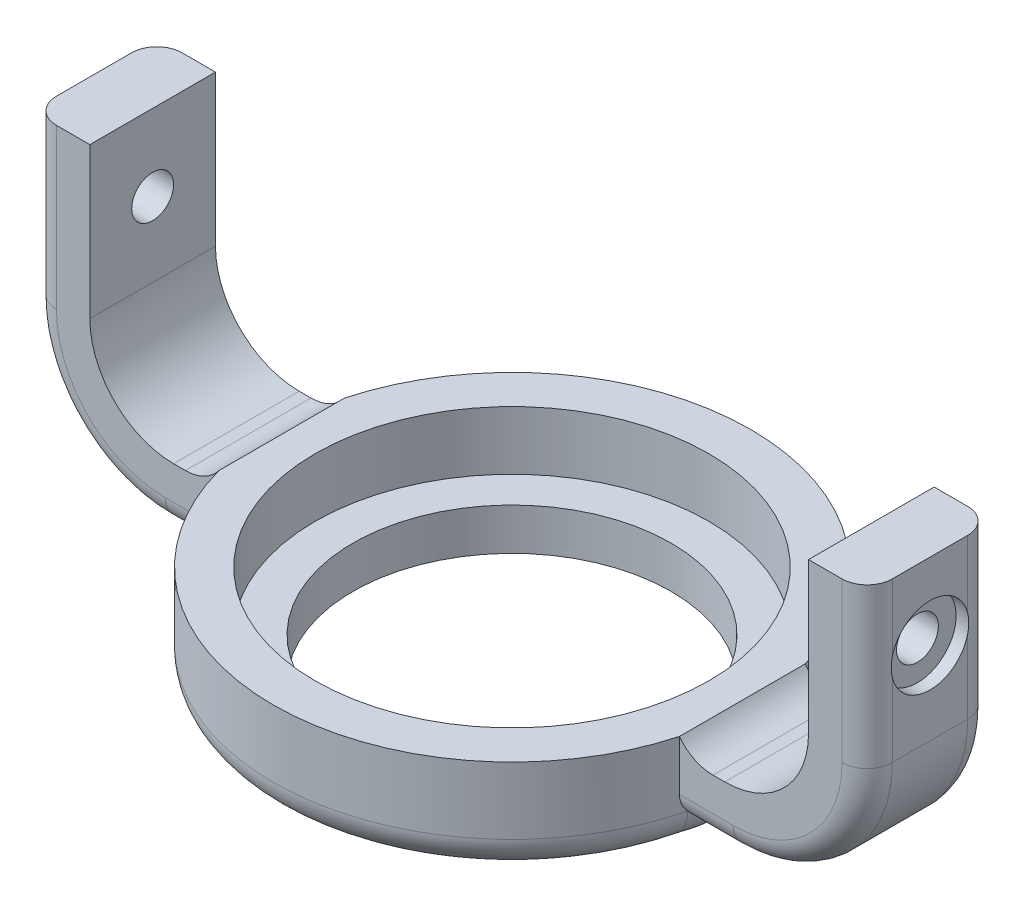
SolidWorks part; units mm, degrees
ref_plane "Front Plane" through (0, 0, 0) normal (0, 0, 1) x (1, 0, 0)
ref_plane "Top Plane" through (0, 0, 0) normal (0, 1, 0) x (1, 0, 0)
ref_plane "Right Plane" through (0, 0, 0) normal (1, 0, 0) x (0, 0, -1)
sketch "Sketch1" plane through (0, 0, 0) normal (0, 1, 0) x (1, 0, 0)
  circle A0 centre (0, 0) radius 23.5
  circle A1 centre (0, 0) radius 28.5
  dimension "D1" = 47
  dimension "D2" = 57
extrude "Boss-Extrude1" add sketch "Sketch1" along normal blind 12
ref_plane "Plane1" through (0, 3, 0) normal (0, -1, 0) x (-1, 0, 0)
sketch "Sketch2" plane through (0, 3, 0) normal (0, 1, 0) x (1, 0, 0)
  line L0 (-49.91, 7.5) -> (-27.4955, 7.5)
  line L2 (-49.91, 7.5) -> (-49.91, -7.5)
  line L4 (49.91, 7.5) -> (49.91, -7.5)
  line L5 (-49.91, -7.5) -> (-27.4955, -7.5)
  line L6 (49.91, 7.5) -> (27.4955, 7.5)
  line L7 (49.91, -7.5) -> (27.4955, -7.5)
  circle A0 centre (0, 0) radius 28.5 construction
  arc A1 (-27.4955, 7.5) -> (-27.4955, -7.5) centre (0, 0) ccw
  arc A2 (27.4955, -7.5) -> (27.4955, 7.5) centre (0, 0) ccw
  point P6 (-49.91, 0)
  point P14 (49.91, 0)
  dimension "D1" = 15
  dimension "D2" = 49.91
  dimension "D3" = 49.91
  dimension "D4" = 15
extrude "Boss-Extrude2" add sketch "Sketch2" along normal through all separate body
sketch "Sketch3" plane through (0, 12, 0) normal (0, 1, 0) x (1, 0, 0)
  line L0 (-49.91, -7.5) -> (-27.4955, -7.5) construction
  line L1 (-49.91, 7.5) -> (-42.91, 7.5)
  line L2 (-49.91, 7.5) -> (-49.91, -7.5)
  line L3 (-49.91, -7.5) -> (-42.91, -7.5)
  line L4 (-42.91, 7.5) -> (-42.91, -7.5)
  line L5 (49.91, -7.5) -> (49.91, 7.5) construction
  line L6 (49.91, 7.5) -> (42.91, 7.5)
  line L7 (49.91, 7.5) -> (49.91, -7.5)
  line L8 (49.91, -7.5) -> (42.91, -7.5)
  line L9 (42.91, 7.5) -> (42.91, -7.5)
  line L10 (49.91, 7.5) -> (27.4955, 7.5) construction
  line L11 (27.4955, -7.5) -> (49.91, -7.5) construction
  dimension "D1" = 42.91
  dimension "D2" = 42.91
extrude "Boss-Extrude4" add sketch "Sketch3" along normal blind 26
sketch "Sketch4" plane through (-49.91, 0, 0) normal (-1, 0, 0) x (0, 0, 1)
  line L0 (-7.5, 3) -> (7.5, 3) construction
  circle A0 centre (0, 28.88) radius 2.5
  dimension "D1" = 5
  dimension "D2" = 25.88
extrude "Cut-Extrude1" cut sketch "Sketch4" against normal through all
sketch "Sketch5" plane through (0, 0, 7.5) normal (0, 0, 1) x (1, 0, 0)
  line L0 (-27.4955, 12) -> (-27.4955, 3) construction
  line L1 (-42.91, 12) -> (-27.4955, 12)
  line L2 (-42.91, 12) -> (-42.91, 10)
  line L3 (-42.91, 10) -> (-27.4955, 10)
  line L4 (-27.4955, 12) -> (-27.4955, 10)
  line L5 (42.91, 38) -> (42.91, 12) construction
  line L6 (27.4955, 12) -> (42.91, 12)
  line L7 (27.4955, 12) -> (27.4955, 10)
  line L8 (27.4955, 10) -> (42.91, 10)
  line L9 (42.91, 12) -> (42.91, 10)
  line L10 (27.4955, 12) -> (42.91, 12) construction
  dimension "D1" = 2
  dimension "D2" = 2
extrude "Cut-Extrude2" cut sketch "Sketch5" against normal through all
sketch "Sketch6" plane through (0, 0, 0) normal (0, -1, 0) x (1, 0, 0)
  circle A0 centre (0, 0) radius 23.5
  circle A1 centre (0, 0) radius 23.5 construction
  circle A2 centre (0, 0) radius 19
  dimension "D1" = 38
extrude "Boss-Extrude5" add sketch "Sketch6" against normal blind 5 separate body
combine bodies "Combine1" operation type add bodies to combine 110 113 111 112
fillet "Fillet7" radius 10 2 edges at (42.91, 10, 0) (-42.91, 10, 0)
fillet "Fillet8" radius 16 2 edges at (49.91, 3, 0) (-49.91, 3, 0)
fillet "Fillet9" radius 3 12 edges at (30.7027, 3, 7.5) (49.91, 28.5, 7.5) (30.7027, 3, -7.5) (45.2237, 7.6863, -7.5) (-49.91, 28.5, 7.5) (-30.7027, 3, 7.5) (-30.7027, 3, -7.5) (-49.91, 28.5, -7.5) (45.2237, 7.6863, 7.5) (49.91, 28.5, -7.5) (-45.2237, 7.6863, 7.5) (-45.2237, 7.6863, -7.5)
fillet "Fillet10" radius 4 1 edges at (0, 0, 28.5)
fillet "Fillet13" radius 5 2 edges at (27.4955, 10, 0) (-27.4955, 10, 0)
sketch "Sketch7" plane through (-49.91, 0, 0) normal (-1, 0, 0) x (0, 0, 1)
  circle A0 centre (0, 28.88) radius 4.625
  dimension "D1" = 9.25
extrude "Cut-Extrude3" cut sketch "Sketch7" against normal blind 1.5
sketch "Sketch8" plane through (49.91, 0, 0) normal (1, 0, 0) x (0, 0, -1)
  circle A0 centre (0, 28.88) radius 4.625
  dimension "D1" = 9.25
extrude "Cut-Extrude4" cut sketch "Sketch8" against normal blind 1.5
